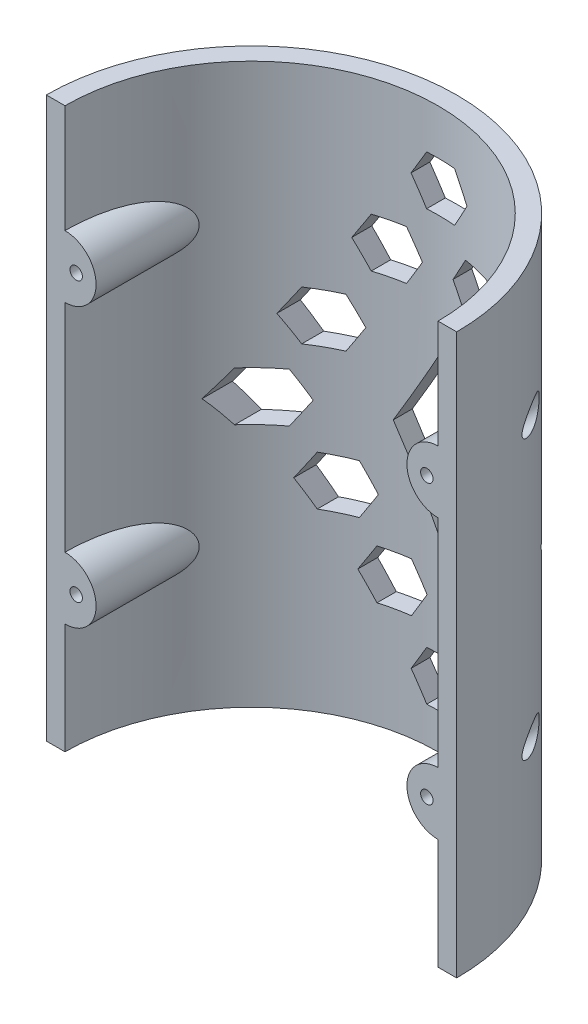
SolidWorks part; units mm, degrees
other "DetailItem1"
other "DetailItem2"
other "DetailItem3"
other "DetailItem4"
other "DetailItem5"
other "DetailItem6"
other "DetailItem7"
other "DetailItem8"
ref_plane "Front Plane" through (0, 0, 0) normal (0, 0, 1) x (1, 0, 0)
ref_plane "Top Plane" through (0, 0, 0) normal (0, 1, 0) x (1, 0, 0)
ref_plane "Right Plane" through (0, 0, 0) normal (1, 0, 0) x (0, 0, -1)
sketch "Sketch1" plane through (0, 0, 0) normal (0, 1, 0) x (1, 0, 0)
  line L0 (-30, 0) -> (-33, 0)
  line L1 (30, 0) -> (33, 0)
  arc A0 (33, 0) -> (-33, 0) centre (0, 0) ccw
  arc A1 (30, 0) -> (-30, 0) centre (0, 0) ccw
extrude "Boss-Extrude1" add sketch "Sketch1" along normal blind 90
ref_plane "Plane1" through (0, 0, -2) normal (0, 0, 1) x (1, 0, 0)
sketch "Sketch7" plane through (0, 0, 0) normal (0, 0, 1) x (1, 0, 0)
  line L0 (-30, 90) -> (-30, 67.6) construction
  line L1 (-30, 90) -> (-30, 0) construction
  line L2 (-30, 67.6) -> (-30, 46.2263) construction
  line L3 (-30, 46.2263) -> (-30, 22.8) construction
  line L4 (-30, 62.6) -> (-30, 72.6)
  line L5 (-30, 27.8) -> (-30, 17.8)
  line L6 (-33, 90) -> (-30, 90) construction
  arc A0 (-30, 62.6) -> (-30, 72.6) centre (-30, 67.6) ccw
  arc A2 (-30, 17.8) -> (-30, 27.8) centre (-30, 22.8) ccw
  dimension "D1" = 22.4
  dimension "D2" = 44.8
  dimension "D3" = 5
  dimension "D4" = 5
extrude "Boss-Extrude3" add sketch "Sketch7" against normal up to surface up to face at (0, 45, -15)
sketch "Sketch8" plane through (0, 0, -2) normal (0, 0, 1) x (1, 0, 0)
  line L0 (-30, 72.6) -> (-30, 62.6) construction
  line L1 (-30, 62.6) -> (-30, 27.8) construction
  line L2 (-30, 27.8) -> (-30, 17.8) construction
  line L3 (-33, 90) -> (-30, 90) construction
  circle A0 centre (-28.2, 67.6) radius 1
  circle A1 centre (-28.2, 22.8) radius 1
  dimension "D1" = 2
  dimension "D2" = 1.8
  dimension "D3" = 1.8
  dimension "D4" = 22.4
  dimension "D5" = 44.8
extrude "Cut-Extrude1" cut sketch "Sketch8" along normal blind 12
sketch "Sketch9" plane through (0, 0, -2) normal (0, 0, 1) x (1, 0, 0)
  line L0 (-30, 90) -> (-30, 72.6) construction
  line L1 (-30, 62.6) -> (-30, 27.8) construction
  line L2 (-33, 90) -> (-30, 90) construction
  circle A0 centre (-28.2, 67.6) radius 2
  circle A1 centre (-28.2, 22.8) radius 2
  dimension "D1" = 22.4
  dimension "D2" = 44.8
  dimension "D3" = 1.8
  dimension "D4" = 1.8
  dimension "D5" = 4
  dimension "D6" = 4
ref_plane "Plane3" through (0, 0, 0) normal (1, 0, 0) x (0, 0, -1)
mirror "Mirror3" about plane through (0, 0, 0) normal (1, 0, 0) of "Boss-Extrude1", "Boss-Extrude3", "Cut-Extrude1"
extrude "Cut-Extrude3" cut sketch "Sketch9" against normal blind 23
mirror "Mirror4" about plane through (0, 0, 0) normal (1, 0, 0) of "Cut-Extrude3"
ref_plane "Plane4" through (0, 0, -33) normal (0, 0, 1) x (1, 0, 0)
sketch "Sketch10" plane through (0, 0, -33) normal (0, 0, 1) x (1, 0, 0)
  line L0 (7.3346, 56.0779) -> (10.563, 61.6697)
  line L8 (63.323, 77.1893) -> (63.3202, 77.1941)
  line L10 (10.563, 61.6697) -> (10.5597, 61.6755)
  line L13 (99.7361, 63.8714) -> (102.4264, 59.2116)
  line L15 (-5.9505, 78.7379) -> (-2.7221, 84.3297)
  line L47 (63.3202, 77.1941) -> (63.323, 77.1893)
  line L52 (99.7361, 63.8714) -> (94.3373, 63.8714)
  line L53 (102.4264, 59.2116) -> (107.8071, 59.2116)
  line L54 (11.1121, 61.6813) -> (11.1054, 61.6697)
  line L55 (17.0416, 61.6697) -> (10.563, 61.6697)
  line L60 (-2.7221, 84.3297) -> (-2.7254, 84.3355)
  line L89 (-2.173, 84.3413) -> (-2.1797, 84.3297)
  line L93 (3.7565, 84.3297) -> (-2.7221, 84.3297)
  line L110 (116.0363, 54.5022) -> (118.7267, 49.8423)
  line L117 (110.6375, 54.5022) -> (110.6347, 54.507)
  line L122 (107.9472, 49.8423) -> (110.6375, 54.5022)
  line L123 (116.0363, 54.5022) -> (110.6375, 54.5022)
  line L124 (110.6375, 54.5022) -> (107.9472, 49.8423)
  line L125 (116.0363, 45.1922) -> (118.7267, 40.5323)
  line L128 (118.7267, 49.8423) -> (124.1074, 49.8423)
  line L129 (124.1074, 49.8423) -> (124.1102, 49.8472)
  line L135 (110.6375, 45.1922) -> (107.9472, 49.852)
  line L152 (110.6347, 54.507) -> (110.6375, 54.5022)
  line L153 (110.6375, 54.5022) -> (116.0363, 54.5022)
  line L156 (68.7038, 77.199) -> (63.323, 77.199)
  line L157 (63.323, 77.199) -> (63.3202, 77.1941)
  line L159 (-2.7254, 84.3355) -> (-2.7221, 84.3297)
  line L160 (116.0363, 45.1922) -> (110.6375, 45.1922)
  line L162 (-2.7221, 84.3297) -> (3.7565, 84.3297)
  line L164 (118.7267, 40.5323) -> (124.1074, 40.5323)
  line L165 (124.1074, 40.5323) -> (126.7978, 45.1922)
  line L166 (125.2302, 45.1922) -> (123.3236, 48.4944)
  line L167 (123.3236, 48.4944) -> (119.5105, 48.4944)
  line L170 (96.471, 82.2454) -> (96.4738, 82.2406)
  line L171 (119.5105, 48.4944) -> (117.6039, 45.1922)
  line L173 (117.6039, 45.1922) -> (119.5105, 41.8899)
  line L174 (119.5105, 41.8899) -> (123.3236, 41.8899)
  line L175 (123.3236, 41.8899) -> (125.2302, 45.1922)
  line L176 (117.141, 49.852) -> (115.2344, 53.1543)
  line L177 (115.2344, 53.1543) -> (111.4213, 53.1543)
  line L178 (111.4213, 53.1543) -> (109.5148, 49.852)
  line L179 (109.5148, 49.852) -> (111.4213, 46.5498)
  line L180 (111.4213, 46.5498) -> (115.2344, 46.5498)
  line L181 (115.2344, 46.5498) -> (117.141, 49.852)
  line L182 (118.7267, 49.852) -> (116.0183, 54.5118)
  line L183 (116.0183, 54.5118) -> (110.6375, 54.5118)
  line L184 (110.6375, 54.5118) -> (107.9472, 49.852)
  line L197 (107.9472, 49.852) -> (110.6375, 45.1922)
  line L198 (110.6375, 45.1922) -> (116.0363, 45.1922)
  line L199 (94.3373, 63.8714) -> (99.7361, 63.8714)
  line L200 (116.0363, 45.1922) -> (118.7267, 49.852)
  line L201 (96.471, 82.2454) -> (96.4738, 82.2503)
  line L203 (126.7978, 45.1922) -> (124.1074, 49.852)
  line L204 (124.1074, 49.852) -> (118.7267, 49.852)
  line L205 (118.7267, 49.852) -> (116.0363, 45.1922)
  line L206 (132.1966, 45.1922) -> (126.7978, 45.1922)
  line L216 (124.1074, 49.852) -> (126.7978, 45.1922)
  line L217 (126.7978, 45.1922) -> (132.1966, 45.1922)
  line L221 (-2.7221, 73.1577) -> (-5.9505, 78.7495)
  line L232 (118.7267, 40.5323) -> (116.0183, 45.1922)
  line L236 (96.4738, 82.2503) -> (96.471, 82.2454)
  line L239 (126.7978, 35.8725) -> (124.1074, 40.5323)
  line L240 (124.1074, 40.5323) -> (118.7267, 40.5323)
  line L243 (132.1966, 35.8725) -> (126.7978, 35.8725)
  line L250 (133.3013, 40.402) -> (131.3947, 43.7043)
  line L251 (131.3947, 43.7043) -> (127.5816, 43.7043)
  line L252 (127.5816, 43.7043) -> (125.675, 40.402)
  line L253 (125.675, 40.402) -> (127.5816, 37.0998)
  line L254 (127.5816, 37.0998) -> (131.3947, 37.0998)
  line L255 (131.3947, 37.0998) -> (133.3013, 40.402)
  line L256 (134.887, 40.5323) -> (132.1785, 45.1922)
  line L257 (132.1785, 45.1922) -> (126.7978, 45.1922)
  line L258 (126.7978, 45.1922) -> (124.1074, 40.5323)
  line L259 (124.1074, 40.5323) -> (126.7978, 35.8725)
  line L260 (126.7978, 35.8725) -> (132.1966, 35.8725)
  line L261 (132.1966, 35.8725) -> (134.887, 40.5323)
  line L262 (3.7565, 73.1577) -> (-2.7221, 73.1577)
  line L267 (5.0821, 78.7495) -> (2.7942, 82.7122)
  line L274 (132.1841, 35.8725) -> (132.1785, 35.8822)
  line L275 (132.1785, 35.8822) -> (126.7978, 35.8822)
  line L276 (126.7978, 35.8822) -> (126.795, 35.8773)
  line L280 (2.7942, 82.7122) -> (-1.7815, 82.7122)
  line L281 (-1.7815, 82.7122) -> (-4.0694, 78.7495)
  line L282 (-4.0694, 78.7495) -> (-1.7815, 74.7868)
  line L283 (-1.7815, 74.7868) -> (2.7942, 74.7868)
  line L284 (2.7942, 74.7868) -> (5.0821, 78.7495)
  line L293 (6.9849, 78.7495) -> (3.7348, 84.3413)
  line L294 (3.7348, 84.3413) -> (-2.7221, 84.3413)
  line L295 (-2.7221, 84.3413) -> (-5.9505, 78.7495)
  line L296 (-5.9505, 78.7495) -> (-2.7221, 73.1577)
  line L297 (-2.7221, 73.1577) -> (3.7565, 73.1577)
  line L300 (3.7565, 73.1577) -> (6.9849, 78.7495)
  line L301 (10.5597, 61.6755) -> (10.563, 61.6697)
  line L302 (99.7361, 54.5517) -> (102.4264, 49.8919)
  line L304 (102.4264, 49.8919) -> (107.8071, 49.8919)
  line L308 (107.8071, 49.8919) -> (110.4975, 54.5517)
  line L309 (108.9299, 54.4214) -> (107.0233, 57.7236)
  line L310 (107.0233, 57.7236) -> (103.2102, 57.7236)
  line L323 (103.2102, 57.7236) -> (101.3037, 54.4214)
  line L324 (101.3037, 54.4214) -> (103.2102, 51.1191)
  line L326 (103.2102, 51.1191) -> (107.0233, 51.1191)
  line L327 (107.0233, 51.1191) -> (108.9299, 54.4214)
  line L328 (102.4264, 59.2116) -> (99.718, 63.8714)
  line L329 (99.7361, 54.5517) -> (102.4264, 59.2116)
  line L342 (110.4975, 54.5517) -> (107.8071, 59.2116)
  line L347 (107.8071, 59.2116) -> (102.4264, 59.2116)
  line L354 (102.4264, 59.2116) -> (99.7361, 54.5517)
  line L361 (116.0183, 45.1922) -> (110.6375, 45.1922)
  line L362 (10.563, 61.6697) -> (17.0416, 61.6697)
  line L365 (115.8963, 54.5517) -> (110.4975, 54.5517)
  line L366 (102.4264, 49.9016) -> (99.718, 54.5614)
  line L381 (10.563, 50.4977) -> (7.3346, 56.0895)
  line L394 (3.7348, 73.1577) -> (-2.7221, 73.1577)
  line L397 (107.8071, 59.2116) -> (110.4975, 54.5517)
  line L398 (110.4975, 54.5517) -> (115.8963, 54.5517)
  line L401 (102.4236, 49.8967) -> (102.4264, 49.9016)
  line L407 (107.8099, 49.8967) -> (107.8071, 49.9016)
  line L408 (107.8071, 49.9016) -> (102.4264, 49.9016)
  line L415 (102.4264, 49.9016) -> (102.4236, 49.8967)
  line L416 (115.8839, 54.5517) -> (115.8782, 54.5614)
  line L417 (115.8782, 54.5614) -> (110.4975, 54.5614)
  line L418 (110.4975, 54.5614) -> (107.8071, 49.9016)
  line L419 (107.8071, 49.9016) -> (107.8099, 49.8967)
  line L420 (94.3373, 54.5517) -> (91.6469, 59.2116)
  line L421 (99.7361, 54.5517) -> (94.3373, 54.5517)
  line L423 (100.8407, 59.0812) -> (98.9342, 62.3835)
  line L424 (98.9342, 62.3835) -> (95.1211, 62.3835)
  line L426 (95.1211, 62.3835) -> (93.2145, 59.0812)
  line L427 (93.2145, 59.0812) -> (95.1211, 55.779)
  line L434 (95.1211, 55.779) -> (98.9342, 55.779)
  line L435 (98.9342, 55.779) -> (100.8407, 59.0812)
  line L436 (99.718, 63.8714) -> (94.3373, 63.8714)
  line L437 (94.3373, 63.8714) -> (91.6469, 59.2116)
  line L438 (91.6469, 59.2116) -> (94.3373, 54.5517)
  line L440 (94.3373, 54.5517) -> (99.7361, 54.5517)
  line L441 (99.718, 54.5614) -> (94.3373, 54.5614)
  line L442 (94.3373, 54.5614) -> (94.3345, 54.5566)
  line L446 (17.0416, 50.4977) -> (10.563, 50.4977)
  line L447 (18.3672, 56.0895) -> (16.0793, 60.0522)
  line L460 (16.0793, 60.0522) -> (11.5036, 60.0522)
  line L461 (13.6996, 44.7825) -> (16.928, 50.3743)
  line L468 (16.928, 50.3743) -> (16.9246, 50.3801)
  line L481 (17.4771, 50.386) -> (17.4704, 50.3743)
  line L482 (23.4066, 50.3743) -> (16.928, 50.3743)
  line L484 (16.9246, 50.3801) -> (16.928, 50.3743)
  line L502 (16.928, 50.3743) -> (23.4066, 50.3743)
  line L503 (16.928, 39.2023) -> (13.6996, 44.7941)
  line L510 (23.4066, 39.2023) -> (16.928, 39.2023)
  line L524 (24.7322, 44.7941) -> (22.4443, 48.7568)
  line L545 (0.6383, 67.1126) -> (3.8667, 72.7044)
  line L546 (3.8667, 72.7044) -> (3.8634, 72.7102)
  line L547 (4.4158, 72.716) -> (4.4091, 72.7044)
  line L548 (10.3453, 72.7044) -> (3.8667, 72.7044)
  line L549 (3.8634, 72.7102) -> (3.8667, 72.7044)
  line L550 (3.8667, 72.7044) -> (10.3453, 72.7044)
  line L551 (3.8667, 61.5324) -> (0.6383, 67.1242)
  line L552 (10.3453, 61.5324) -> (3.8667, 61.5324)
  line L553 (11.6709, 67.1242) -> (9.383, 71.0869)
  line L554 (9.383, 71.0869) -> (4.8073, 71.0869)
  line L555 (4.8073, 71.0869) -> (2.5194, 67.1242)
  line L556 (2.5194, 67.1242) -> (4.8073, 63.1615)
  line L557 (4.8073, 63.1615) -> (9.383, 63.1615)
  line L558 (9.383, 63.1615) -> (11.6709, 67.1242)
  line L559 (13.5737, 67.1242) -> (10.3236, 72.716)
  line L560 (10.3236, 72.716) -> (3.8667, 72.716)
  line L561 (3.8667, 72.716) -> (0.6383, 67.1242)
  line L562 (0.6383, 67.1242) -> (3.8667, 61.5324)
  line L563 (10.3453, 61.5324) -> (13.5737, 67.1242)
  line L564 (11.5036, 60.0522) -> (9.2157, 56.0895)
  line L565 (9.2157, 56.0895) -> (11.5036, 52.1268)
  line L566 (11.5036, 52.1268) -> (16.0793, 52.1268)
  line L567 (16.0793, 52.1268) -> (18.3672, 56.0895)
  line L568 (20.27, 56.0895) -> (17.0199, 61.6813)
  line L569 (17.0199, 61.6813) -> (10.563, 61.6813)
  line L570 (10.563, 61.6813) -> (7.3346, 56.0895)
  line L571 (7.3346, 56.0895) -> (10.563, 50.4977)
  line L572 (17.0416, 50.4977) -> (20.27, 56.0895)
  line L573 (22.4443, 48.7568) -> (17.8686, 48.7568)
  line L574 (17.8686, 48.7568) -> (15.5807, 44.7941)
  line L575 (15.5807, 44.7941) -> (17.8686, 40.8314)
  line L576 (17.8686, 40.8314) -> (22.4443, 40.8314)
  line L577 (22.4443, 40.8314) -> (24.7322, 44.7941)
  line L578 (26.635, 44.7941) -> (23.3849, 50.386)
  line L579 (23.3849, 50.386) -> (16.928, 50.386)
  line L580 (16.928, 50.386) -> (13.6996, 44.7941)
  line L581 (13.6996, 44.7941) -> (16.928, 39.2023)
  line L582 (16.928, 39.2023) -> (23.4066, 39.2023)
  line L583 (23.4066, 39.2023) -> (26.635, 44.7941)
  line L584 (23.3849, 39.2023) -> (16.928, 39.2023)
  line L585 (7.3346, 32.5763) -> (10.563, 38.1682)
  line L586 (10.563, 38.1682) -> (10.5597, 38.174)
  line L587 (11.1121, 38.1798) -> (11.1054, 38.1682)
  line L588 (17.0416, 38.1682) -> (10.563, 38.1682)
  line L589 (10.5597, 38.174) -> (10.563, 38.1682)
  line L590 (10.563, 38.1682) -> (17.0416, 38.1682)
  line L591 (10.563, 26.9962) -> (7.3346, 32.588)
  line L592 (17.0416, 26.9962) -> (10.563, 26.9962)
  line L593 (18.3672, 32.588) -> (16.0793, 36.5507)
  line L594 (16.0793, 36.5507) -> (11.5036, 36.5507)
  line L595 (11.5036, 36.5507) -> (9.2157, 32.588)
  line L596 (9.2157, 32.588) -> (11.5036, 28.6253)
  line L597 (11.5036, 28.6253) -> (16.0793, 28.6253)
  line L598 (16.0793, 28.6253) -> (18.3672, 32.588)
  line L599 (20.27, 32.588) -> (17.0199, 38.1798)
  line L600 (17.0199, 38.1798) -> (10.563, 38.1798)
  line L601 (10.563, 38.1798) -> (7.3346, 32.588)
  line L602 (7.3346, 32.588) -> (10.563, 26.9962)
  line L603 (10.563, 26.9962) -> (17.0416, 26.9962)
  line L604 (17.0416, 26.9962) -> (20.27, 32.588)
  line L605 (17.0199, 26.9962) -> (10.563, 26.9962)
  line L606 (1.1208, 21.3243) -> (4.3492, 26.9161)
  line L607 (4.3492, 26.9161) -> (4.3458, 26.9219)
  line L608 (4.8983, 26.9277) -> (4.8916, 26.9161)
  line L609 (10.8278, 26.9161) -> (4.3492, 26.9161)
  line L610 (4.3458, 26.9219) -> (4.3492, 26.9161)
  line L611 (4.3492, 26.9161) -> (10.8278, 26.9161)
  line L612 (4.3492, 15.7441) -> (1.1208, 21.3359)
  line L613 (10.8278, 15.7441) -> (4.3492, 15.7441)
  line L614 (12.1534, 21.3359) -> (9.8655, 25.2986)
  line L615 (9.8655, 25.2986) -> (5.2898, 25.2986)
  line L616 (5.2898, 25.2986) -> (3.0019, 21.3359)
  line L617 (3.0019, 21.3359) -> (5.2898, 17.3732)
  line L618 (5.2898, 17.3732) -> (9.8655, 17.3732)
  line L619 (9.8655, 17.3732) -> (12.1534, 21.3359)
  line L620 (14.0562, 21.3359) -> (10.8061, 26.9277)
  line L621 (10.8061, 26.9277) -> (4.3492, 26.9277)
  line L622 (4.3492, 26.9277) -> (1.1208, 21.3359)
  line L623 (1.1208, 21.3359) -> (4.3492, 15.7441)
  line L624 (4.3492, 15.7441) -> (10.8278, 15.7441)
  line L625 (10.8278, 15.7441) -> (14.0562, 21.3359)
  line L626 (10.8061, 15.7441) -> (4.3492, 15.7441)
  line L627 (-5.9328, 9.7364) -> (-2.7043, 15.3282)
  line L628 (-2.7043, 15.3282) -> (-2.7077, 15.334)
  line L629 (-2.1552, 15.3398) -> (-2.1619, 15.3282)
  line L630 (3.7742, 15.3282) -> (-2.7043, 15.3282)
  line L631 (-2.7077, 15.334) -> (-2.7043, 15.3282)
  line L632 (-2.7043, 15.3282) -> (3.7742, 15.3282)
  line L633 (-2.7043, 4.1562) -> (-5.9328, 9.748)
  line L634 (3.7742, 4.1562) -> (-2.7043, 4.1562)
  line L635 (5.0998, 9.748) -> (2.812, 13.7107)
  line L636 (2.812, 13.7107) -> (-1.7638, 13.7107)
  line L637 (-1.7638, 13.7107) -> (-4.0516, 9.748)
  line L638 (-4.0516, 9.748) -> (-1.7638, 5.7853)
  line L639 (-1.7638, 5.7853) -> (2.812, 5.7853)
  line L640 (2.812, 5.7853) -> (5.0998, 9.748)
  line L641 (7.0027, 9.748) -> (3.7525, 15.3398)
  line L642 (3.7525, 15.3398) -> (-2.7043, 15.3398)
  line L643 (-2.7043, 15.3398) -> (-5.9328, 9.748)
  line L644 (-5.9328, 9.748) -> (-2.7043, 4.1562)
  line L645 (-2.7043, 4.1562) -> (3.7742, 4.1562)
  line L646 (3.7742, 4.1562) -> (7.0027, 9.748)
  line L647 (3.7525, 4.1562) -> (-2.7043, 4.1562)
  line L648 (-12.7465, 21.0485) -> (-9.518, 26.6403)
  line L649 (-9.518, 26.6403) -> (-9.5214, 26.6461)
  line L650 (-8.9689, 26.6519) -> (-8.9756, 26.6403)
  line L651 (-3.0395, 26.6403) -> (-9.518, 26.6403)
  line L652 (-9.5214, 26.6461) -> (-9.518, 26.6403)
  line L653 (-9.518, 26.6403) -> (-3.0395, 26.6403)
  line L654 (-9.518, 15.4683) -> (-12.7465, 21.0601)
  line L655 (-3.0395, 15.4683) -> (-9.518, 15.4683)
  line L656 (-1.7139, 21.0601) -> (-4.0017, 25.0228)
  line L657 (-4.0017, 25.0228) -> (-8.5775, 25.0228)
  line L658 (-8.5775, 25.0228) -> (-10.8653, 21.0601)
  line L659 (-10.8653, 21.0601) -> (-8.5775, 17.0974)
  line L660 (-8.5775, 17.0974) -> (-4.0017, 17.0974)
  line L661 (-4.0017, 17.0974) -> (-1.7139, 21.0601)
  line L662 (0.189, 21.0601) -> (-3.0612, 26.6519)
  line L663 (-3.0612, 26.6519) -> (-9.518, 26.6519)
  line L664 (-9.518, 26.6519) -> (-12.7465, 21.0601)
  line L665 (-12.7465, 21.0601) -> (-9.518, 15.4683)
  line L666 (-9.518, 15.4683) -> (-3.0395, 15.4683)
  line L667 (-3.0395, 15.4683) -> (0.189, 21.0601)
  line L668 (-3.0612, 15.4683) -> (-9.518, 15.4683)
  line L669 (-19.4279, 32.2283) -> (-16.1995, 37.8201)
  line L670 (-16.1995, 37.8201) -> (-16.2028, 37.8259)
  line L671 (-15.6503, 37.8317) -> (-15.657, 37.8201)
  line L672 (-9.7209, 37.8201) -> (-16.1995, 37.8201)
  line L673 (-16.2028, 37.8259) -> (-16.1995, 37.8201)
  line L674 (-16.1995, 37.8201) -> (-9.7209, 37.8201)
  line L675 (-16.1995, 26.6481) -> (-19.4279, 32.2399)
  line L676 (-9.7209, 26.6481) -> (-16.1995, 26.6481)
  line L677 (-8.3953, 32.2399) -> (-10.6832, 36.2026)
  line L678 (-10.6832, 36.2026) -> (-15.2589, 36.2026)
  line L679 (-15.2589, 36.2026) -> (-17.5468, 32.2399)
  line L680 (-17.5468, 32.2399) -> (-15.2589, 28.2772)
  line L681 (-15.2589, 28.2772) -> (-10.6832, 28.2772)
  line L682 (-10.6832, 28.2772) -> (-8.3953, 32.2399)
  line L683 (-6.4925, 32.2399) -> (-9.7426, 37.8317)
  line L684 (-9.7426, 37.8317) -> (-16.1995, 37.8317)
  line L685 (-16.1995, 37.8317) -> (-19.4279, 32.2399)
  line L686 (-19.4279, 32.2399) -> (-16.1995, 26.6481)
  line L687 (-16.1995, 26.6481) -> (-9.7209, 26.6481)
  line L688 (-9.7209, 26.6481) -> (-6.4925, 32.2399)
  line L689 (-9.7426, 26.6481) -> (-16.1995, 26.6481)
  line L690 (-26.6981, 43.3394) -> (-23.4697, 48.9312)
  line L691 (-23.4697, 48.9312) -> (-23.473, 48.937)
  line L692 (-22.9206, 48.9428) -> (-22.9273, 48.9312)
  line L693 (-16.9911, 48.9312) -> (-23.4697, 48.9312)
  line L694 (-23.473, 48.937) -> (-23.4697, 48.9312)
  line L695 (-23.4697, 48.9312) -> (-16.9911, 48.9312)
  line L696 (-23.4697, 37.7592) -> (-26.6981, 43.351)
  line L697 (-16.9911, 37.7592) -> (-23.4697, 37.7592)
  line L698 (-15.6655, 43.351) -> (-17.9534, 47.3137)
  line L699 (-17.9534, 47.3137) -> (-22.5291, 47.3137)
  line L700 (-22.5291, 47.3137) -> (-24.817, 43.351)
  line L701 (-24.817, 43.351) -> (-22.5291, 39.3883)
  line L702 (-22.5291, 39.3883) -> (-17.9534, 39.3883)
  line L703 (-17.9534, 39.3883) -> (-15.6655, 43.351)
  line L704 (-13.7627, 43.351) -> (-17.0128, 48.9428)
  line L705 (-17.0128, 48.9428) -> (-23.4697, 48.9428)
  line L706 (-23.4697, 48.9428) -> (-26.6981, 43.351)
  line L707 (-26.6981, 43.351) -> (-23.4697, 37.7592)
  line L708 (-23.4697, 37.7592) -> (-16.9911, 37.7592)
  line L709 (-16.9911, 37.7592) -> (-13.7627, 43.351)
  line L710 (-17.0128, 37.7592) -> (-23.4697, 37.7592)
  line L711 (-20.9599, 54.9525) -> (-17.7314, 60.5443)
  line L712 (-17.7314, 60.5443) -> (-17.7348, 60.5502)
  line L713 (-17.1823, 60.556) -> (-17.189, 60.5443)
  line L714 (-11.2528, 60.5443) -> (-17.7314, 60.5443)
  line L715 (-17.7348, 60.5502) -> (-17.7314, 60.5443)
  line L716 (-17.7314, 60.5443) -> (-11.2528, 60.5443)
  line L717 (-17.7314, 49.3723) -> (-20.9599, 54.9642)
  line L718 (-11.2528, 49.3723) -> (-17.7314, 49.3723)
  line L719 (-9.9272, 54.9642) -> (-12.2151, 58.9269)
  line L720 (-12.2151, 58.9269) -> (-16.7908, 58.9269)
  line L721 (-16.7908, 58.9269) -> (-19.0787, 54.9642)
  line L722 (-19.0787, 54.9642) -> (-16.7908, 51.0015)
  line L723 (-16.7908, 51.0015) -> (-12.2151, 51.0015)
  line L724 (-12.2151, 51.0015) -> (-9.9272, 54.9642)
  line L725 (-8.0244, 54.9642) -> (-11.2745, 60.556)
  line L726 (-11.2745, 60.556) -> (-17.7314, 60.556)
  line L727 (-17.7314, 60.556) -> (-20.9599, 54.9642)
  line L728 (-20.9599, 54.9642) -> (-17.7314, 49.3723)
  line L729 (-17.7314, 49.3723) -> (-11.2528, 49.3723)
  line L730 (-11.2528, 49.3723) -> (-8.0244, 54.9642)
  line L731 (-11.2745, 49.3723) -> (-17.7314, 49.3723)
  line L732 (-13.4455, 67.0201) -> (-10.217, 72.6119)
  line L733 (-10.217, 72.6119) -> (-10.2204, 72.6177)
  line L734 (-9.6679, 72.6235) -> (-9.6746, 72.6119)
  line L735 (-3.7385, 72.6119) -> (-10.217, 72.6119)
  line L736 (-10.2204, 72.6177) -> (-10.217, 72.6119)
  line L737 (-10.217, 72.6119) -> (-3.7385, 72.6119)
  line L738 (-10.217, 61.4399) -> (-13.4455, 67.0317)
  line L739 (-3.7385, 61.4399) -> (-10.217, 61.4399)
  line L740 (-2.4129, 67.0317) -> (-4.7007, 70.9944)
  line L741 (-4.7007, 70.9944) -> (-9.2765, 70.9944)
  line L742 (-9.2765, 70.9944) -> (-11.5643, 67.0317)
  line L743 (-11.5643, 67.0317) -> (-9.2765, 63.069)
  line L744 (-9.2765, 63.069) -> (-4.7007, 63.069)
  line L745 (-4.7007, 63.069) -> (-2.4129, 67.0317)
  line L746 (-0.51, 67.0317) -> (-3.7602, 72.6235)
  line L747 (-3.7602, 72.6235) -> (-10.217, 72.6235)
  line L748 (-10.217, 72.6235) -> (-13.4455, 67.0317)
  line L749 (-13.4455, 67.0317) -> (-10.217, 61.4399)
  line L750 (-10.217, 61.4399) -> (-3.7385, 61.4399)
  line L751 (-3.7385, 61.4399) -> (-0.51, 67.0317)
  line L752 (-3.7602, 61.4399) -> (-10.217, 61.4399)
  line L757 (7.3259, 43.4089) -> (0.0622, 30.3507)
  line L758 (7.3259, 43.4089) -> (0.7712, 56.4092)
  line L759 (0.0622, 30.3507) -> (-6.4925, 43.351)
  line L760 (0.7712, 56.4092) -> (-6.4925, 43.351)
  line L762 (63.3582, 15.6711) -> (77.8491, 15.6711)
  line L763 (63.3582, 15.6711) -> (63.3582, 41.8899)
  line L764 (63.3582, 41.8899) -> (77.8491, 41.8899)
  line L765 (77.8491, 15.6711) -> (77.8491, 41.8899)
  line L766 (63.3582, 15.6711) -> (77.8491, 41.8899) construction
  line L767 (63.3582, 41.8899) -> (77.8491, 15.6711) construction
  point P32 (70.6036, 28.7805)
extrude "Cut-Extrude11" cut sketch "Sketch10" along normal through all contours L758 L760 L759 L757 | L576 L577 L524 L573 L574 L575 | L566 L567 L447 L460 L564 L565 | L557 L558 L553 L554 L555 L556 | L283 L284 L267 L280 L281 L282 | L744 L745 L740 L741 L742 L743 | L723 L724 L719 L720 L721 L722 | L702 L703 L698 L699 L700 L701 | L681 L682 L677 L678 L679 L680 | L660 L661 L656 L657 L658 L659 | L639 L640 L635 L636 L637 L638 | L618 L619 L614 L615 L616 L617 | L597 L598 L593 L594 L595 L596 region at (0.5063, 78.7495, -33) region at (13.7914, 56.0895, -33) region at (20.1564, 44.7941, -33) region at (7.0951, 67.1242, -33) region at (13.7914, 32.588, -33) region at (7.5776, 21.3359, -33) region at (0.5241, 9.748, -33) region at (-6.2896, 21.0601, -33) region at (-12.971, 32.2399, -33) region at (-20.2412, 43.351, -33) region at (-14.503, 54.9642, -33) region at (-6.9886, 67.0317, -33) region at (0.4167, 43.38, -33)
